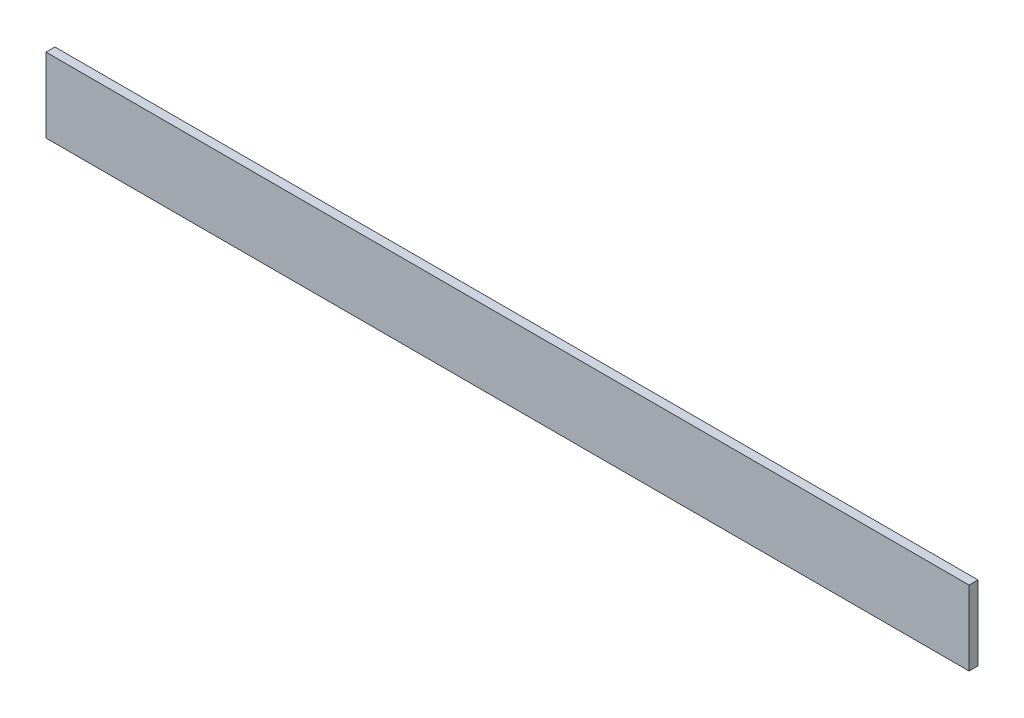
SolidWorks part; units mm, degrees
ref_plane "Спереди" through (0, 0, 0) normal (0, 0, 1) x (1, 0, 0)
ref_plane "Сверху" through (0, 0, 0) normal (0, 1, 0) x (1, 0, 0)
ref_plane "Справа" through (0, 0, 0) normal (1, 0, 0) x (0, 0, -1)
sketch "Эскиз1" plane through (0, 0, 0) normal (1, 0, 0) x (0, 0, -1)
  line L0 (0, 0) -> (25, 0)
  line L1 (0, 0) -> (0, 25)
extrude "Вытянуть-Тонкостенный1" add sketch "Эскиз1" along normal blind 310 thin thin type one direction wall 3
sketch "Эскиз2" plane through (0, 0, 0) normal (0, -1, 0) x (1, 0, 0)
  line L1 (288, -25) -> (310, -25)
  line L2 (288, -25) -> (288, -3)
  line L3 (288, -3) -> (310, -3)
  line L4 (310, -25) -> (310, -3)
extrude "Вырез-Вытянуть1" cut sketch "Эскиз2" against normal through all
